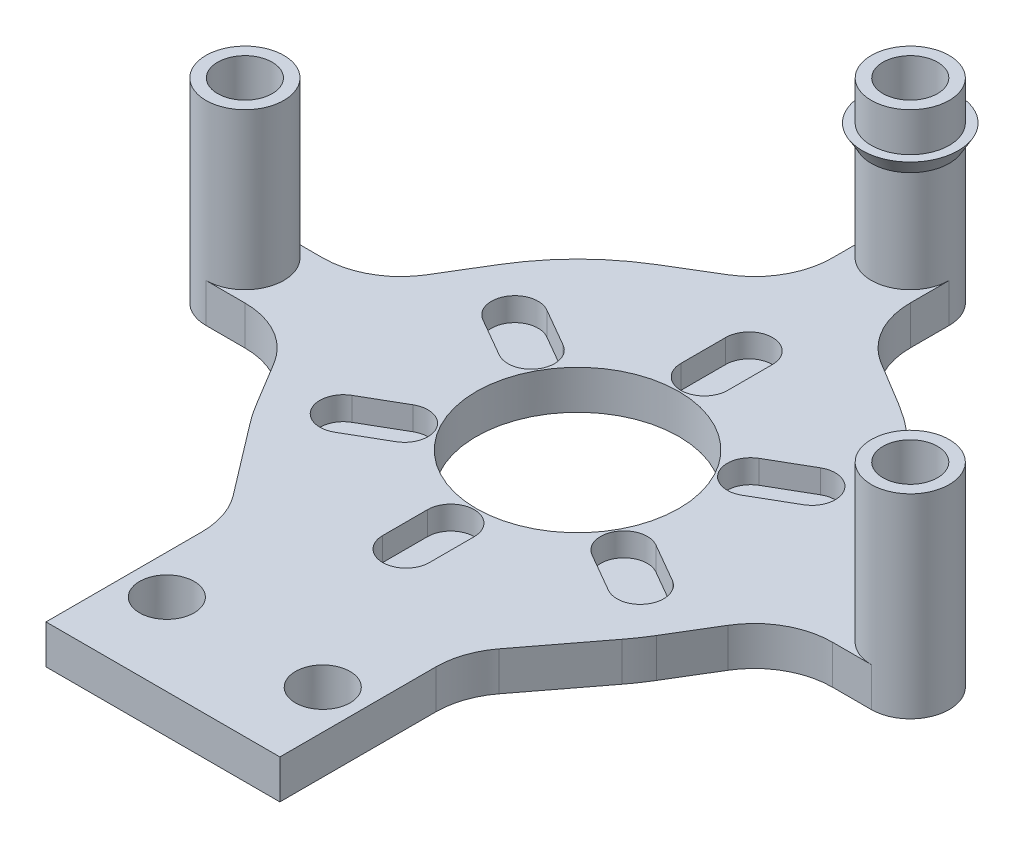
SolidWorks part; units mm, degrees
ref_plane "Front Plane" through (0, 0, 0) normal (0, 0, 1) x (1, 0, 0)
ref_plane "Top Plane" through (0, 0, 0) normal (0, 1, 0) x (1, 0, 0)
ref_plane "Right Plane" through (0, 0, 0) normal (1, 0, 0) x (0, 0, -1)
sketch "Esquisse1" plane through (0, 0, 0) normal (0, 1, 0) x (1, 0, 0)
  line L0 (-3, 16.25) -> (-3, 22)
  line L1 (3, 22) -> (3, 16.25)
  line L2 (0, -55) -> (0, 55) construction
  line L3 (12.5729, 10.7231) -> (17.5526, 13.5981)
  line L4 (20.5526, 8.4019) -> (15.5729, 5.5269)
  line L5 (15.5729, -5.5269) -> (20.5526, -8.4019)
  line L6 (17.5526, -13.5981) -> (12.5729, -10.7231)
  line L7 (3, -16.25) -> (3, -22)
  line L8 (-3, -22) -> (-3, -16.25)
  line L9 (-12.5729, -10.7231) -> (-17.5526, -13.5981)
  line L10 (-20.5526, -8.4019) -> (-15.5729, -5.5269)
  line L11 (-15.5729, 5.5269) -> (-20.5526, 8.4019)
  line L12 (-17.5526, 13.5981) -> (-12.5729, 10.7231)
  line L13 (0, 25) -> (6.5383, 25) construction
  line L14 (0, 30) -> (6.5383, 30) construction
  circle A0 centre (0, 0) radius 30
  circle A1 centre (0, 0) radius 13
  arc A2 (-3, 16.25) -> (3, 16.25) centre (0, 16.25) ccw
  arc A3 (3, 22) -> (-3, 22) centre (0, 22) ccw
  arc A4 (20.5526, 8.4019) -> (17.5526, 13.5981) centre (19.0526, 11) ccw
  arc A5 (12.5729, 10.7231) -> (15.5729, 5.5269) centre (14.0729, 8.125) ccw
  arc A6 (17.5526, -13.5981) -> (20.5526, -8.4019) centre (19.0526, -11) ccw
  arc A7 (15.5729, -5.5269) -> (12.5729, -10.7231) centre (14.0729, -8.125) ccw
  arc A8 (-3, -22) -> (3, -22) centre (0, -22) ccw
  arc A9 (3, -16.25) -> (-3, -16.25) centre (0, -16.25) ccw
  arc A10 (-20.5526, -8.4019) -> (-17.5526, -13.5981) centre (-19.0526, -11) ccw
  arc A11 (-12.5729, -10.7231) -> (-15.5729, -5.5269) centre (-14.0729, -8.125) ccw
  arc A12 (-17.5526, 13.5981) -> (-20.5526, 8.4019) centre (-19.0526, 11) ccw
  arc A13 (-15.5729, 5.5269) -> (-12.5729, 10.7231) centre (-14.0729, 8.125) ccw
  point P45 (0, 0)
  dimension "D1" = 60
  dimension "D2" = 26
  dimension "D4" = 3
  dimension "D5" = 5
  dimension "D3" = 5.75
  dimension "D6" = 6
extrude "Boss.-Extru.1" add sketch "Esquisse1" along normal blind 3
sketch "Esquisse2" plane through (0, 0, 0) normal (0, -1, 0) x (1, 0, 0)
  circle A0 centre (0, 0) radius 30
  circle A1 centre (0, 0) radius 30 construction
  circle A2 centre (0, 0) radius 13
  circle A3 centre (0, 0) radius 13 construction
extrude "Boss.-Extru.2" add sketch "Esquisse2" along normal blind 2
sketch "Esquisse3" plane through (0, 3, 0) normal (0, 1, 0) x (1, 0, 0)
  line L0 (-15, -33.1859) -> (-15, -53.1859)
  line L1 (-15, -53.1859) -> (15, -53.1859)
  line L2 (15, -53.1859) -> (15, -33.1859)
  line L3 (0, 0) -> (0, -49.6378) construction
  line L4 (-23.8595, -18.1859) -> (-17.0468, -27.1239)
  line L5 (23.8595, -18.1859) -> (17.0468, -27.1239)
  line L6 (-10, -46.1859) -> (10, -46.1859) construction
  line L7 (37.6732, 5) -> (42.6732, 5)
  line L9 (42.6732, -5) -> (37.6732, -5)
  line L10 (0, 0) -> (57.2295, 0) construction
  line L11 (25.6732, -15.5205) -> (29.1155, -9.8265)
  line L12 (25.6732, 15.5205) -> (29.1155, 9.8265)
  line L13 (-5, 37.6732) -> (-5, 42.6732)
  line L14 (5, 42.6732) -> (5, 37.6732)
  line L15 (15.5205, 25.6732) -> (9.8265, 29.1155)
  line L16 (-15.5205, 25.6732) -> (-9.8265, 29.1155)
  line L17 (-37.6732, -5) -> (-42.6732, -5)
  line L18 (-42.6732, 5) -> (-37.6732, 5)
  line L19 (-25.6732, 15.5205) -> (-29.1155, 9.8265)
  line L20 (-25.6732, -15.5205) -> (-29.1155, -9.8265)
  circle A0 centre (0, 0) radius 30 construction
  arc A2 (-15, -33.1859) -> (-17.0468, -27.1239) centre (-25, -33.1859) ccw
  arc A3 (15, -33.1859) -> (17.0468, -27.1239) centre (25, -33.1859) cw
  arc A4 (-23.8595, -18.1859) -> (23.8595, -18.1859) centre (0, 0) ccw
  circle A5 centre (-10, -42.6859) radius 3.5
  circle A6 centre (10, -42.6859) radius 3.5
  arc A7 (37.6732, 5) -> (29.1155, 9.8265) centre (37.6732, 15) cw
  arc A8 (37.6732, -5) -> (29.1155, -9.8265) centre (37.6732, -15) ccw
  arc A9 (42.6732, -5) -> (42.6732, 5) centre (42.6732, 0) ccw
  arc A10 (25.6732, 15.5205) -> (25.6732, -15.5205) centre (0, 0) cw
  arc A11 (-5, 37.6732) -> (-9.8265, 29.1155) centre (-15, 37.6732) cw
  arc A12 (5, 37.6732) -> (9.8265, 29.1155) centre (15, 37.6732) ccw
  arc A13 (5, 42.6732) -> (-5, 42.6732) centre (0, 42.6732) ccw
  arc A14 (-15.5205, 25.6732) -> (15.5205, 25.6732) centre (0, 0) cw
  arc A15 (-37.6732, -5) -> (-29.1155, -9.8265) centre (-37.6732, -15) cw
  arc A16 (-37.6732, 5) -> (-29.1155, 9.8265) centre (-37.6732, 15) ccw
  arc A17 (-42.6732, 5) -> (-42.6732, -5) centre (-42.6732, 0) ccw
  arc A18 (-25.6732, -15.5205) -> (-25.6732, 15.5205) centre (0, 0) cw
  point P59 (0, 0)
  dimension "D1" = 10
  dimension "D2" = 10
  dimension "D4" = 20
  dimension "D6" = 7
  dimension "D8" = 20
  dimension "D10" = 10
  dimension "D11" = 10
  dimension "D13" = 12
  dimension "D14" = 3
  dimension "D3" = 30
  dimension "D5" = 15
  dimension "D7" = 7
  dimension "D9" = 10
  dimension "D12" = 5
extrude "Boss.-Extru.3" add sketch "Esquisse3" against normal up to surface (5 mm away) up to face at (0, -2, -30)
sketch "Esquisse4" plane through (0, 3, 0) normal (0, 1, 0) x (1, 0, 0)
  circle A0 centre (-42.6732, 0) radius 5
  circle A1 centre (42.6732, 0) radius 5
  circle A3 centre (0, 42.6732) radius 5
  arc A4 (-42.6732, 5) -> (-42.6732, -5) centre (-42.6732, 0) ccw construction
extrude "Boss.-Extru.4" add sketch "Esquisse4" along normal blind 20
sketch "Esquisse5" plane through (0, 23, 0) normal (0, 1, 0) x (1, 0, 0)
  circle A0 centre (-42.6732, 0) radius 3.5
  circle A1 centre (42.6732, 0) radius 3.5
  circle A2 centre (0, 42.6732) radius 3.5
  circle A3 centre (-42.6732, 0) radius 5 construction
  circle A4 centre (0, 42.6732) radius 5 construction
  circle A5 centre (42.6732, 0) radius 5 construction
  dimension "D1" = 7
extrude "Enlèv. mat.-Extru.1" cut sketch "Esquisse5" against normal through all
ref_plane "Plan1" through (0, 0, -42.6732) normal (0, 0, 1) x (1, 0, 0)
sketch "Esquisse6" plane through (0, 0, -42.6732) normal (0, 0, 1) x (1, 0, 0)
  line L0 (5, 16) -> (6.1547, 18)
  line L1 (5, 3) -> (5, 23) construction
  line L2 (6.1547, 18) -> (5, 18)
  line L3 (5, 18) -> (5, 16)
  line L7 (5, 13) -> (18.8005, 13) construction
  line L9 (5, 3) -> (-5, 3) construction
  line L10 (3.5, 23) -> (-3.5, 23) construction
  line L11 (5, 23) -> (-5, 23) construction
  point P4 (6.3961, 23.7829)
  point P6 (5, 18.8732)
  point P8 (6.5532, 21.4262)
  point P10 (7.6807, 9.7435)
  dimension "D1" = 2
  dimension "D2" = 5
  dimension "D3" = 30
ref_axis "Axe1" through (0, -2, -42.6732) along (0, 1, 0)
revolve "Révolution1" add sketch "Esquisse6" angle 360 about axis through (0, -2, -42.6732) along (0, 1, 0)
